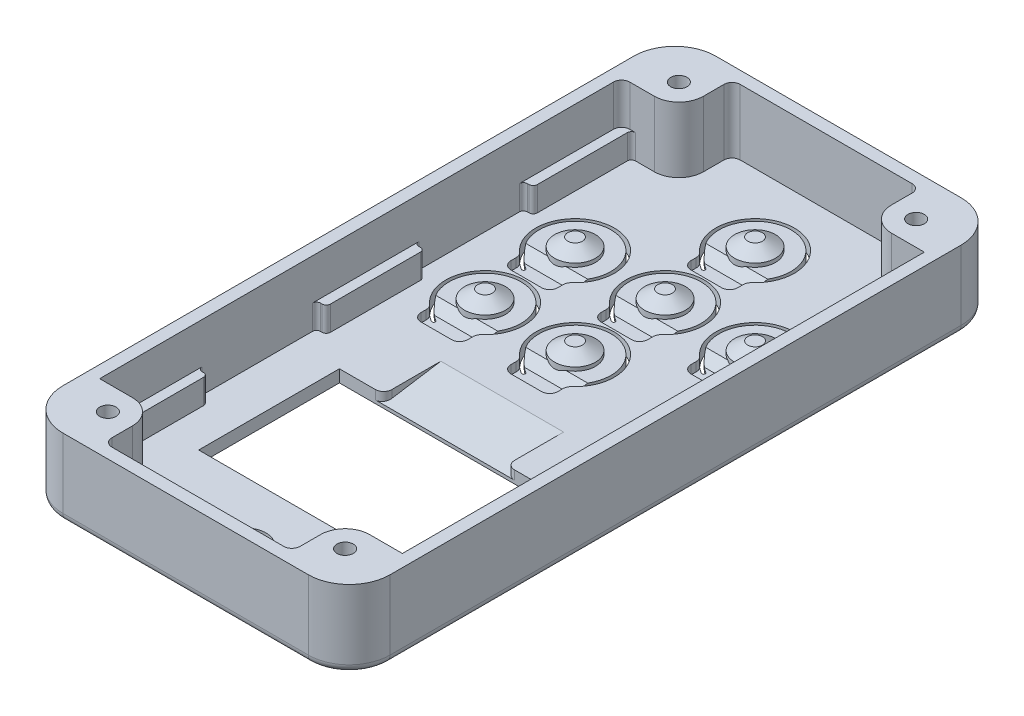
SolidWorks part; units mm, degrees
ref_plane "Front Plane" through (0, 0, 0) normal (0, 0, 1) x (1, 0, 0)
ref_plane "Top Plane" through (0, 0, 0) normal (0, 1, 0) x (1, 0, 0)
ref_plane "Right Plane" through (0, 0, 0) normal (1, 0, 0) x (0, 0, -1)
sketch "Base Sketch" plane through (0, 0, 0) normal (0, 1, 0) x (1, 0, 0)
  line L0 (0, 0) -> (40, 0)
  line L1 (40, 0) -> (40, 79.79)
  line L2 (40, 79.79) -> (0, 79.79)
  line L3 (0, 79.79) -> (0, 0)
extrude "Base" add sketch "Base Sketch" along normal blind 9.5
fillet "Corner Rounds R5" radius 5 4 edges at (0, 4.75, -79.79) (40, 4.75, -79.79) (40, 4.75, 0) (0, 4.75, 0)
shell "Shell 1.5" thickness 1.5 removed face at (20, 9.5, -39.895)
sketch "Boss Sketch" plane through (0, 0, 0) normal (0, 1, 0) x (1, 0, 0)
  line L0 (1.5, 1.5) -> (8.5, 1.5)
  line L1 (8.5, 1.5) -> (8.5, 5)
  line L2 (5.5, 8) -> (1.5, 8)
  line L3 (1.5, 8) -> (1.5, 1.5)
  line L4 (38.5, 1.5) -> (31.5, 1.5)
  line L5 (31.5, 1.5) -> (31.5, 5)
  line L6 (34.5, 8) -> (38.5, 8)
  line L7 (38.5, 8) -> (38.5, 1.5)
  line L16 (1.5, 78.29) -> (8.5, 78.29)
  line L17 (8.5, 78.29) -> (8.5, 74.79)
  line L18 (5.5, 71.79) -> (1.5, 71.79)
  line L19 (1.5, 71.79) -> (1.5, 78.29)
  line L20 (38.5, 78.29) -> (31.5, 78.29)
  line L21 (31.5, 78.29) -> (31.5, 74.79)
  line L22 (34.5, 71.79) -> (38.5, 71.79)
  line L23 (38.5, 71.79) -> (38.5, 78.29)
  arc A0 (8.5, 5) -> (5.5, 8) centre (5.4999, 4.9999) ccw
  circle A1 centre (5.5, 5) radius 1
  arc A2 (31.5, 5) -> (34.5, 8) centre (34.5001, 4.9999) cw
  circle A3 centre (34.5, 5) radius 1
  circle A5 centre (5.5, 74.79) radius 1
  circle A7 centre (34.5, 74.79) radius 1
  arc A8 (8.5, 74.79) -> (5.5, 71.79) centre (5.4999, 74.7901) cw
  arc A9 (31.5, 74.79) -> (34.5, 71.79) centre (34.5001, 74.7901) ccw
extrude "Corner Bosses + M2 Pilot Holes" add sketch "Boss Sketch" along normal blind 9.5
sketch "Ledge Sketch" plane through (0, 0, 0) normal (0, 1, 0) x (1, 0, 0)
  line L0 (1.5, 8) -> (2.7, 8)
  line L1 (2.7, 8) -> (2.7, 20)
  line L2 (2.7, 20) -> (1.5, 20)
  line L3 (1.5, 20) -> (1.5, 8)
  line L4 (37.3, 8) -> (38.5, 8)
  line L5 (38.5, 8) -> (38.5, 20)
  line L6 (38.5, 20) -> (37.3, 20)
  line L7 (37.3, 20) -> (37.3, 8)
  line L8 (1.5, 34.5) -> (2.7, 34.5)
  line L9 (2.7, 34.5) -> (2.7, 46.5)
  line L10 (2.7, 46.5) -> (1.5, 46.5)
  line L11 (1.5, 46.5) -> (1.5, 34.5)
  line L12 (37.3, 34.5) -> (38.5, 34.5)
  line L13 (38.5, 34.5) -> (38.5, 46.5)
  line L14 (38.5, 46.5) -> (37.3, 46.5)
  line L15 (37.3, 46.5) -> (37.3, 34.5)
  line L16 (1.5, 59.79) -> (2.7, 59.79)
  line L17 (2.7, 59.79) -> (2.7, 71.79)
  line L18 (2.7, 71.79) -> (1.5, 71.79)
  line L19 (1.5, 71.79) -> (1.5, 59.79)
  line L20 (37.3, 59.79) -> (38.5, 59.79)
  line L21 (38.5, 59.79) -> (38.5, 71.79)
  line L22 (38.5, 71.79) -> (37.3, 71.79)
  line L23 (37.3, 71.79) -> (37.3, 59.79)
extrude "Side Ledges" add sketch "Ledge Sketch" along normal blind 4.5
fillet "Outer Face Round R1" radius 1 8 edges at (1.4645, 0, -1.4645) (20, 0, 0) (38.5355, 0, -1.4645) (40, 0, -39.895) (38.5355, 0, -78.3255) (20, 0, -79.79) (1.4645, 0, -78.3255) (0, 0, -39.895)
sketch "Window Sketch" plane through (0, 0, 0) normal (0, 1, 0) x (1, 0, 0)
  line L0 (7.1, 14.5) -> (32.9, 14.5)
  line L1 (32.9, 14.5) -> (32.9, 31.7)
  line L2 (32.9, 31.7) -> (7.1, 31.7)
  line L3 (7.1, 31.7) -> (7.1, 14.5)
extrude "Display Window" cut sketch "Window Sketch" along normal through all
ref_plane "Mid Plane X20" through (20, 0, 0) normal (1, 0, 0) x (0, 0, -1)
sketch "Ramp Sketch" plane through (20, 0, 0) normal (1, 0, 0) x (0, 0, -1)
  line L0 (31, 0.4) -> (31.7, 0.4)
  line L1 (31.7, 0.4) -> (38.7, 1.5)
  line L2 (38.7, 1.5) -> (38.7, 2.5)
  line L3 (38.7, 2.5) -> (31, 2.5)
  line L4 (31, 2.5) -> (31, 0.4)
extrude "Cable Ramp" cut sketch "Ramp Sketch" against normal blind 7.5 and the other way blind 7.5
ref_plane "Plate Inner Face" through (0, 1.5, 0) normal (0, 1, 0) x (1, 0, 0)
sketch "LED Window Sketch" plane through (0, 1.5, 0) normal (0, 1, 0) x (1, 0, 0)
  circle A0 centre (20, 7.28) radius 2.5598
  point P2 (0, 0)
extrude "LED Window" cut sketch "LED Window Sketch" against normal blind 1.3
sketch "Plunger Stems Sketch" plane through (0, 1.5, 0) normal (0, 1, 0) x (1, 0, 0)
  circle A0 centre (9, 47.6) radius 2.5
  circle A1 centre (20, 47.6) radius 2.5
  circle A2 centre (9, 58.6) radius 2.5
  circle A3 centre (20, 58.6) radius 2.5
  circle A4 centre (31, 58.6) radius 2.5
  circle A5 centre (20, 69.6) radius 2.5
extrude "Plunger Stems 5.0" add sketch "Plunger Stems Sketch" along normal blind 0.45
ref_plane "Plunger Cone Base" through (0, 1.95, 0) normal (0, 1, 0) x (1, 0, 0)
sketch "Plunger Cone Sketch" plane through (0, 1.95, 0) normal (0, 1, 0) x (1, 0, 0)
  circle A0 centre (9, 47.6) radius 2.5
  circle A1 centre (20, 47.6) radius 2.5
  circle A2 centre (9, 58.6) radius 2.5
  circle A3 centre (20, 58.6) radius 2.5
  circle A4 centre (31, 58.6) radius 2.5
  circle A5 centre (20, 69.6) radius 2.5
extrude "Plunger Cones to 1.8" add sketch "Plunger Cone Sketch" along normal blind 1 draft 57.995
fillet "Boss Junction Fillets R1" radius 1 8 edges at (1.5, 7, -71.79) (37.3, 3, -71.79) (37.3, 3, -8) (2.7, 3, -8) (31.5, 5.5, -78.29) (8.5, 5.5, -78.29) (31.5, 5.5, -1.5) (8.5, 5.5, -1.5)
sketch "C-Slot Sketch" plane through (0, 0, 0) normal (0, 1, 0) x (1, 0, 0)
  arc A0 (10.4434, 43.0222) -> (7.5566, 43.0222) centre (9, 47.6) ccw
  arc A1 (7.5566, 43.0222) -> (7.6769, 43.4036) centre (7.6168, 43.2129) ccw
  arc A2 (7.6769, 43.4036) -> (10.3231, 43.4036) centre (9, 47.6) cw
  arc A3 (10.3231, 43.4036) -> (10.4434, 43.0222) centre (10.3832, 43.2129) ccw
  arc A4 (21.4434, 43.0222) -> (18.5566, 43.0222) centre (20, 47.6) ccw
  arc A5 (18.5566, 43.0222) -> (18.6769, 43.4036) centre (18.6168, 43.2129) ccw
  arc A6 (18.6769, 43.4036) -> (21.3231, 43.4036) centre (20, 47.6) cw
  arc A7 (21.3231, 43.4036) -> (21.4434, 43.0222) centre (21.3832, 43.2129) ccw
  arc A8 (10.4434, 54.0222) -> (7.5566, 54.0222) centre (9, 58.6) ccw
  arc A9 (7.5566, 54.0222) -> (7.6769, 54.4036) centre (7.6168, 54.2129) ccw
  arc A10 (7.6769, 54.4036) -> (10.3231, 54.4036) centre (9, 58.6) cw
  arc A11 (10.3231, 54.4036) -> (10.4434, 54.0222) centre (10.3832, 54.2129) ccw
  arc A12 (21.4434, 54.0222) -> (18.5566, 54.0222) centre (20, 58.6) ccw
  arc A13 (18.5566, 54.0222) -> (18.6769, 54.4036) centre (18.6168, 54.2129) ccw
  arc A14 (18.6769, 54.4036) -> (21.3231, 54.4036) centre (20, 58.6) cw
  arc A15 (21.3231, 54.4036) -> (21.4434, 54.0222) centre (21.3832, 54.2129) ccw
  arc A16 (32.4434, 54.0222) -> (29.5566, 54.0222) centre (31, 58.6) ccw
  arc A17 (29.5566, 54.0222) -> (29.6769, 54.4036) centre (29.6168, 54.2129) ccw
  arc A18 (29.6769, 54.4036) -> (32.3231, 54.4036) centre (31, 58.6) cw
  arc A19 (32.3231, 54.4036) -> (32.4434, 54.0222) centre (32.3832, 54.2129) ccw
  arc A20 (21.4434, 65.0222) -> (18.5566, 65.0222) centre (20, 69.6) ccw
  arc A21 (18.5566, 65.0222) -> (18.6769, 65.4036) centre (18.6168, 65.2129) ccw
  arc A22 (18.6769, 65.4036) -> (21.3231, 65.4036) centre (20, 69.6) cw
  arc A23 (21.3231, 65.4036) -> (21.4434, 65.0222) centre (21.3832, 65.2129) ccw
sketch "Sketch10" plane through (0, 1.5, 0) normal (0, 1, 0) x (1, 0, 0)
  line L0 (11.864, 44.259) -> (11.864, 41.636)
  line L1 (11.864, 41.636) -> (6.136, 41.636)
  line L2 (6.136, 41.636) -> (6.136, 44.259)
  line L3 (6.136, 44.259) -> (11.864, 44.259)
  line L4 (22.864, 44.259) -> (22.864, 41.636)
  line L5 (22.864, 41.636) -> (17.136, 41.636)
  line L6 (17.136, 41.636) -> (17.136, 44.259)
  line L7 (17.136, 44.259) -> (22.864, 44.259)
  line L8 (11.864, 55.259) -> (11.864, 52.636)
  line L9 (11.864, 52.636) -> (6.136, 52.636)
  line L10 (6.136, 52.636) -> (6.136, 55.259)
  line L11 (6.136, 55.259) -> (11.864, 55.259)
  line L12 (22.864, 55.259) -> (22.864, 52.636)
  line L13 (22.864, 52.636) -> (17.136, 52.636)
  line L14 (17.136, 52.636) -> (17.136, 55.259)
  line L15 (17.136, 55.259) -> (22.864, 55.259)
  line L16 (33.864, 55.259) -> (33.864, 52.636)
  line L17 (33.864, 52.636) -> (28.136, 52.636)
  line L18 (28.136, 52.636) -> (28.136, 55.259)
  line L19 (28.136, 55.259) -> (33.864, 55.259)
  line L20 (22.864, 66.259) -> (22.864, 63.636)
  line L21 (22.864, 63.636) -> (17.136, 63.636)
  line L22 (17.136, 63.636) -> (17.136, 66.259)
  line L23 (17.136, 66.259) -> (22.864, 66.259)
extrude "Cut-Extrude7" cut sketch "Sketch10" against normal blind 1.1
sketch "Sketch11" plane through (0, 0, 0) normal (0, 1, 0) x (1, 0, 0)
  arc A0 (11.4, 43.4431) -> (6.6, 43.4431) centre (9, 47.6) ccw
  arc A1 (6.6, 43.4431) -> (6.8, 43.7895) centre (6.7, 43.6163) ccw
  arc A2 (6.8, 43.7895) -> (11.2, 43.7895) centre (9, 47.6) cw
  arc A3 (11.2, 43.7895) -> (11.4, 43.4431) centre (11.3, 43.6163) ccw
  arc A4 (22.4, 43.4431) -> (17.6, 43.4431) centre (20, 47.6) ccw
  arc A5 (17.6, 43.4431) -> (17.8, 43.7895) centre (17.7, 43.6163) ccw
  arc A6 (17.8, 43.7895) -> (22.2, 43.7895) centre (20, 47.6) cw
  arc A7 (22.2, 43.7895) -> (22.4, 43.4431) centre (22.3, 43.6163) ccw
  arc A8 (11.4, 54.4431) -> (6.6, 54.4431) centre (9, 58.6) ccw
  arc A9 (6.6, 54.4431) -> (6.8, 54.7895) centre (6.7, 54.6163) ccw
  arc A10 (6.8, 54.7895) -> (11.2, 54.7895) centre (9, 58.6) cw
  arc A11 (11.2, 54.7895) -> (11.4, 54.4431) centre (11.3, 54.6163) ccw
  arc A12 (22.4, 54.4431) -> (17.6, 54.4431) centre (20, 58.6) ccw
  arc A13 (17.6, 54.4431) -> (17.8, 54.7895) centre (17.7, 54.6163) ccw
  arc A14 (17.8, 54.7895) -> (22.2, 54.7895) centre (20, 58.6) cw
  arc A15 (22.2, 54.7895) -> (22.4, 54.4431) centre (22.3, 54.6163) ccw
  arc A16 (33.4, 54.4431) -> (28.6, 54.4431) centre (31, 58.6) ccw
  arc A17 (28.6, 54.4431) -> (28.8, 54.7895) centre (28.7, 54.6163) ccw
  arc A18 (28.8, 54.7895) -> (33.2, 54.7895) centre (31, 58.6) cw
  arc A19 (33.2, 54.7895) -> (33.4, 54.4431) centre (33.3, 54.6163) ccw
  arc A20 (22.4, 65.4431) -> (17.6, 65.4431) centre (20, 69.6) ccw
  arc A21 (17.6, 65.4431) -> (17.8, 65.7895) centre (17.7, 65.6163) ccw
  arc A22 (17.8, 65.7895) -> (22.2, 65.7895) centre (20, 69.6) cw
  arc A23 (22.2, 65.7895) -> (22.4, 65.4431) centre (22.3, 65.6163) ccw
extrude "Button C-Slots 300deg 0.4" cut sketch "Sketch11" along normal through all
chamfer "Chamfer1" distance 1.1 angle 45 6 edges at (9, 1.5, -44.259) (20, 1.5, -66.259) (31, 1.5, -55.259) (20, 1.5, -55.259) (9, 1.5, -55.259) (20, 1.5, -44.259)
fillet "Fillet1" radius 1 24 edges at (11.864, 0.95, -43.7481) (11.864, 0.95, -41.636) (6.136, 0.95, -41.636) (6.136, 0.95, -43.7481) (22.864, 0.95, -63.636) (22.864, 0.95, -65.7481) (17.136, 0.95, -63.636) (17.136, 0.95, -65.7481) (33.864, 0.95, -52.636) (33.864, 0.95, -54.7481) (28.136, 0.95, -52.636) (28.136, 0.95, -54.7481) (22.864, 0.95, -52.636) (22.864, 0.95, -54.7481) (17.136, 0.95, -52.636) (17.136, 0.95, -54.7481) (11.864, 0.95, -52.636) (11.864, 0.95, -54.7481) (6.136, 0.95, -52.636) (6.136, 0.95, -54.7481) (22.864, 0.95, -41.636) (22.864, 0.95, -43.7481) (17.136, 0.95, -41.636) (17.136, 0.95, -43.7481)
fillet "Fillet2" radius 0.5 17 edges at (2.7, 3, -71.79) (1.5, 3, -59.79) (2.7, 3, -59.79) (38.5, 3, -59.79) (37.3, 3, -59.79) (38.5, 3, -46.5) (37.3, 3, -46.5) (2.7, 3, -46.5) (1.5, 3, -46.5) (38.5, 3, -34.5) (37.3, 3, -34.5) (2.7, 3, -34.5) (1.5, 3, -34.5) (38.5, 3, -20) (37.3, 3, -20) (2.7, 3, -20) (1.5, 3, -20)
fillet "Fillet3" radius 1 2 edges at (27.5, 0.95, -31.7) (12.5, 0.95, -31.7)
